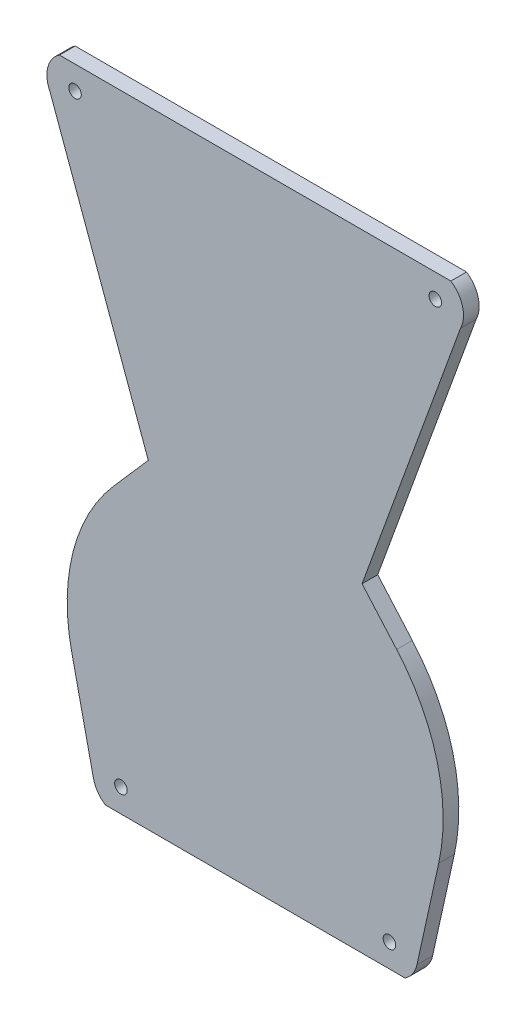
SolidWorks part; units mm, degrees
ref_plane "Front Plane" through (0, 0, 0) normal (0, 0, 1) x (1, 0, 0)
ref_plane "Top Plane" through (0, 0, 0) normal (0, 1, 0) x (1, 0, 0)
ref_plane "Right Plane" through (0, 0, 0) normal (1, 0, 0) x (0, 0, -1)
sketch "Sketch1" plane through (0, 0, 0) normal (0, 0, 1) x (1, 0, 0)
  line L48 (-65.537, 88.4494) -> (-34.1202, 2.1327) construction
  line L49 (-62.4749, 100) -> (-55, 100) construction
  line L50 (-55, 100) -> (55, 100) construction
  line L51 (55, 100) -> (62.4749, 100) construction
  line L52 (34.1202, 2.1327) -> (65.537, 88.4494) construction
  line L53 (-34.1202, 2.1327) -> (-45.1727, -10.5104) construction
  line L54 (-51.6443, -94.4376) -> (-58.5931, -62.917) construction
  line L55 (-40.3553, -100) -> (-47.8303, -100) construction
  line L56 (40.3553, -100) -> (-40.3553, -100) construction
  line L57 (47.8303, -100) -> (40.3553, -100) construction
  line L58 (58.5931, -62.917) -> (51.6443, -94.4376) construction
  line L59 (45.1727, -10.5104) -> (34.1202, 2.1327) construction
  line L60 (45.1727, -10.5104) -> (34.1202, 2.1327)
  line L61 (58.5931, -62.917) -> (51.6443, -94.4376)
  line L62 (47.8303, -100) -> (40.3553, -100)
  line L63 (40.3553, -100) -> (-40.3553, -100)
  line L64 (-40.3553, -100) -> (-47.8303, -100)
  line L65 (-51.6443, -94.4376) -> (-58.5931, -62.917)
  line L66 (-34.1202, 2.1327) -> (-45.1727, -10.5104)
  line L67 (34.1202, 2.1327) -> (65.537, 88.4494)
  line L68 (55, 100) -> (62.4749, 100)
  line L69 (-55, 100) -> (55, 100)
  line L70 (-62.4749, 100) -> (-55, 100)
  line L71 (-65.537, 88.4494) -> (-34.1202, 2.1327)
  circle A36 centre (-57.5, 92.5) radius 2
  circle A37 centre (57.5, 92.5) radius 2
  arc A44 (-62.4749, 100) -> (-65.537, 88.4494) centre (-57.5, 92.5) ccw construction
  arc A45 (65.537, 88.4494) -> (62.4749, 100) centre (57.5, 92.5) ccw construction
  arc A46 (-45.1727, -10.5104) -> (-58.5931, -62.917) centre (0, -50) ccw construction
  arc A47 (-51.6443, -94.4376) -> (-47.8303, -100) centre (-42.8553, -92.5) ccw construction
  circle A48 centre (-42.8553, -92.5) radius 2 construction
  arc A49 (47.8303, -100) -> (51.6443, -94.4376) centre (42.8553, -92.5) ccw construction
  circle A50 centre (42.8553, -92.5) radius 2 construction
  arc A51 (58.5931, -62.917) -> (45.1727, -10.5104) centre (0, -50) ccw construction
  arc A52 (58.5931, -62.917) -> (45.1727, -10.5104) centre (0, -50) ccw
  circle A53 centre (42.8553, -92.5) radius 2
  arc A54 (47.8303, -100) -> (51.6443, -94.4376) centre (42.8553, -92.5) ccw
  circle A55 centre (-42.8553, -92.5) radius 2
  arc A56 (-51.6443, -94.4376) -> (-47.8303, -100) centre (-42.8553, -92.5) ccw
  arc A57 (-45.1727, -10.5104) -> (-58.5931, -62.917) centre (0, -50) ccw
  arc A58 (65.537, 88.4494) -> (62.4749, 100) centre (57.5, 92.5) ccw
  arc A59 (-62.4749, 100) -> (-65.537, 88.4494) centre (-57.5, 92.5) ccw
  dimension "D1" = 4
extrude "Boss-Extrude1" add sketch "Sketch1" along normal blind 5 contours L70 A59 L71 L66 A57 L65 A56 L64 L63 L62 A54 L61 A52 L60 L67 A58 L68 L69 A36 A37 A53 A55 region at (0, 0.8353, 0)
sketch "Sketch2" plane through (0, 0, 0) normal (0, 0, -1) x (-1, 0, 0)
  line L0 (-26.5846, 10.6667) -> (-24.7233, 5.5529) construction
  line L1 (-24.7233, 5.5529) -> (-50, 75) construction
  line L2 (-24.3503, 0) -> (24.3503, 0) construction
  line L3 (-22.7022, 0) -> (22.7022, 0) construction
  line L4 (-26.5846, 10.6667) -> (26.5846, 10.6667) construction
  line L5 (26.5846, 10.6667) -> (24.7233, 5.5529) construction
  line L6 (-23.7479, 0.5) -> (23.7479, 0.5)
  line L7 (25.8705, 10.1667) -> (24.2535, 5.7239)
  line L8 (-25.8705, 10.1667) -> (25.8705, 10.1667)
  line L9 (-25.8705, 10.1667) -> (-24.2535, 5.7239)
  arc A0 (-24.7233, 5.5529) -> (-24.3503, 0) centre (-34.1202, 2.1327) cw construction
  arc A2 (24.7233, 5.5529) -> (24.3503, 0) centre (34.1202, 2.1327) ccw construction
  arc A3 (24.2535, 5.7239) -> (23.7479, 0.5) centre (34.1202, 2.1327) ccw
  arc A4 (-24.2535, 5.7239) -> (-23.7479, 0.5) centre (-34.1202, 2.1327) cw
  point P5 (0, 0)
  point P17 (0, 0)
  point P18 (0, 0)
  dimension "D1" = 0.5
extrude "Boss-Extrude2" add sketch "Sketch2" along normal blind 10 contours L9 A4 L6 A3 L7 L8 region at (0, 5.4128, 0)
chamfer "Chamfer2" distance 10 distance2 10 1 edges at (0, 10.1667, -10)
